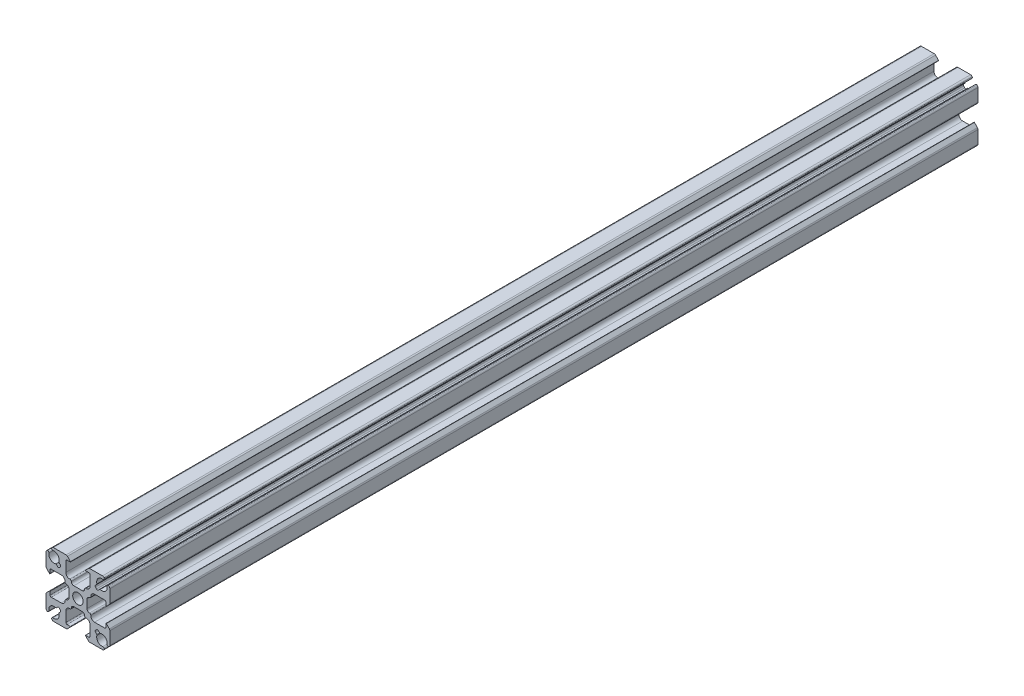
SolidWorks part; units mm, degrees
ref_plane "Front Plane" through (0, 0, 0) normal (0, 0, 1) x (1, 0, 0)
ref_plane "Top Plane" through (0, 0, 0) normal (0, 1, 0) x (1, 0, 0)
ref_plane "Right Plane" through (0, 0, 0) normal (1, 0, 0) x (0, 0, -1)
ref_plane "Plane1" through (0, 0, 0) normal (0, 0, -1) x (-1, 0, 0)
sketch "Sketch1" plane through (0, 0, 0) normal (0, 0, -1) x (-1, 0, 0)
  line L0 (-7.4885, 8.6199) -> (-6.9856, 8.117)
  line L1 (-6.9856, 7.4099) -> (-7.4099, 6.9856)
  line L2 (-8.117, 6.9856) -> (-8.6199, 7.4885)
  line L3 (-12.7, 9.7594) -> (-12.7, 4.7107)
  line L4 (-12.4803, 4.1803) -> (-11.2707, 2.9707)
  line L5 (-11.1, 3.0414) -> (-11.1, 4.325)
  line L6 (-10.6, 4.825) -> (-6.6, 4.825)
  line L7 (-5.1, 3.325) -> (-5.1, 3.15)
  line L8 (-3.6, 1.65) -> (-3.6, -1.65)
  line L9 (-5.1, -3.15) -> (-5.1, -3.325)
  line L10 (-6.6, -4.825) -> (-10.6, -4.825)
  line L11 (-11.1, -4.325) -> (-11.1, -3.0414)
  line L12 (-11.2707, -2.9707) -> (-12.4803, -4.1803)
  line L13 (-12.7, -4.7107) -> (-12.7, -9.7594)
  line L14 (-8.6199, -7.4885) -> (-8.117, -6.9856)
  line L15 (-7.4099, -6.9856) -> (-6.9856, -7.4099)
  line L16 (-6.9856, -8.117) -> (-7.4885, -8.6199)
  line L17 (-9.7594, -12.7) -> (-4.7107, -12.7)
  line L18 (-4.1803, -12.4803) -> (-2.9707, -11.2707)
  line L19 (-3.0414, -11.1) -> (-4.325, -11.1)
  line L20 (-4.825, -10.6) -> (-4.825, -6.6)
  line L21 (-3.325, -5.1) -> (-3.15, -5.1)
  line L22 (-1.65, -3.6) -> (1.65, -3.6)
  line L23 (3.15, -5.1) -> (3.325, -5.1)
  line L24 (4.825, -6.6) -> (4.825, -10.6)
  line L25 (4.325, -11.1) -> (3.0414, -11.1)
  line L26 (2.9707, -11.2707) -> (4.1803, -12.4803)
  line L27 (4.7107, -12.7) -> (9.7594, -12.7)
  line L28 (7.4885, -8.6199) -> (6.9856, -8.117)
  line L29 (6.9856, -7.4099) -> (7.4099, -6.9856)
  line L30 (8.117, -6.9856) -> (8.6199, -7.4885)
  line L31 (12.7, -9.7594) -> (12.7, -4.7107)
  line L32 (12.4803, -4.1803) -> (11.2707, -2.9707)
  line L33 (11.1, -3.0414) -> (11.1, -4.325)
  line L34 (10.6, -4.825) -> (6.6, -4.825)
  line L35 (5.1, -3.325) -> (5.1, -3.15)
  line L36 (3.6, -1.65) -> (3.6, 1.65)
  line L37 (5.1, 3.15) -> (5.1, 3.325)
  line L38 (6.6, 4.825) -> (10.6, 4.825)
  line L39 (11.1, 4.325) -> (11.1, 3.0414)
  line L40 (11.2707, 2.9707) -> (12.4803, 4.1803)
  line L41 (12.7, 4.7107) -> (12.7, 9.7594)
  line L42 (8.6199, 7.4885) -> (8.117, 6.9856)
  line L43 (7.4099, 6.9856) -> (6.9856, 7.4099)
  line L44 (6.9856, 8.117) -> (7.4885, 8.6199)
  line L45 (9.7594, 12.7) -> (4.7107, 12.7)
  line L46 (4.1803, 12.4803) -> (2.9707, 11.2707)
  line L47 (3.0414, 11.1) -> (4.325, 11.1)
  line L48 (4.825, 10.6) -> (4.825, 6.6)
  line L49 (3.325, 5.1) -> (3.15, 5.1)
  line L50 (1.65, 3.6) -> (-1.65, 3.6)
  line L51 (-3.15, 5.1) -> (-3.325, 5.1)
  line L52 (-4.825, 6.6) -> (-4.825, 10.6)
  line L53 (-4.325, 11.1) -> (-3.0414, 11.1)
  line L54 (-2.9707, 11.2707) -> (-4.1803, 12.4803)
  line L55 (-4.7107, 12.7) -> (-9.7594, 12.7)
  circle A0 centre (0, 0) radius 2.08
  arc A1 (-9.7594, 12.7) -> (-10.4266, 12.2927) centre (-9.7594, 11.95) ccw
  arc A2 (-10.4266, 12.2927) -> (-9.8933, 11.5721) centre (-9.9818, 12.0642) ccw
  arc A3 (-9.8933, 11.5721) -> (-7.5492, 8.8748) centre (-9.525, 9.525) cw
  arc A4 (-7.5492, 8.8748) -> (-7.4885, 8.6199) centre (-7.3118, 8.7967) ccw
  arc A5 (-6.9856, 8.117) -> (-6.9856, 7.4099) centre (-7.3392, 7.7635) cw
  arc A6 (-7.4099, 6.9856) -> (-8.117, 6.9856) centre (-7.7635, 7.3392) cw
  arc A7 (-8.6199, 7.4885) -> (-8.8748, 7.5492) centre (-8.7967, 7.3118) ccw
  arc A8 (-8.8748, 7.5492) -> (-11.5721, 9.8933) centre (-9.525, 9.525) cw
  arc A9 (-11.5721, 9.8933) -> (-12.2927, 10.4266) centre (-12.0642, 9.9818) ccw
  arc A10 (-12.2927, 10.4266) -> (-12.7, 9.7594) centre (-11.95, 9.7594) ccw
  arc A11 (-12.7, 4.7107) -> (-12.4803, 4.1803) centre (-11.95, 4.7107) ccw
  arc A12 (-11.2707, 2.9707) -> (-11.1, 3.0414) centre (-11.2, 3.0414) ccw
  arc A13 (-11.1, 4.325) -> (-10.6, 4.825) centre (-10.6, 4.325) cw
  arc A14 (-6.6, 4.825) -> (-5.1, 3.325) centre (-6.6, 3.325) cw
  arc A15 (-5.1, 3.15) -> (-4.6, 2.65) centre (-4.6, 3.15) ccw
  arc A16 (-4.6, 2.65) -> (-3.6, 1.65) centre (-4.6, 1.65) cw
  arc A17 (-3.6, -1.65) -> (-4.6, -2.65) centre (-4.6, -1.65) cw
  arc A18 (-4.6, -2.65) -> (-5.1, -3.15) centre (-4.6, -3.15) ccw
  arc A19 (-5.1, -3.325) -> (-6.6, -4.825) centre (-6.6, -3.325) cw
  arc A20 (-10.6, -4.825) -> (-11.1, -4.325) centre (-10.6, -4.325) cw
  arc A21 (-11.1, -3.0414) -> (-11.2707, -2.9707) centre (-11.2, -3.0414) ccw
  arc A22 (-12.4803, -4.1803) -> (-12.7, -4.7107) centre (-11.95, -4.7107) ccw
  arc A23 (-12.7, -9.7594) -> (-12.2927, -10.4266) centre (-11.95, -9.7594) ccw
  arc A24 (-12.2927, -10.4266) -> (-11.5721, -9.8933) centre (-12.0642, -9.9818) ccw
  arc A25 (-11.5721, -9.8933) -> (-8.8748, -7.5492) centre (-9.525, -9.525) cw
  arc A26 (-8.8748, -7.5492) -> (-8.6199, -7.4885) centre (-8.7967, -7.3118) ccw
  arc A27 (-8.117, -6.9856) -> (-7.4099, -6.9856) centre (-7.7635, -7.3392) cw
  arc A28 (-6.9856, -7.4099) -> (-6.9856, -8.117) centre (-7.3392, -7.7635) cw
  arc A29 (-7.4885, -8.6199) -> (-7.5492, -8.8748) centre (-7.3118, -8.7967) ccw
  arc A30 (-7.5492, -8.8748) -> (-9.8933, -11.5721) centre (-9.525, -9.525) cw
  arc A31 (-9.8933, -11.5721) -> (-10.4266, -12.2927) centre (-9.9818, -12.0642) ccw
  arc A32 (-10.4266, -12.2927) -> (-9.7594, -12.7) centre (-9.7594, -11.95) ccw
  arc A33 (-4.7107, -12.7) -> (-4.1803, -12.4803) centre (-4.7107, -11.95) ccw
  arc A34 (-2.9707, -11.2707) -> (-3.0414, -11.1) centre (-3.0414, -11.2) ccw
  arc A35 (-4.325, -11.1) -> (-4.825, -10.6) centre (-4.325, -10.6) cw
  arc A36 (-4.825, -6.6) -> (-3.325, -5.1) centre (-3.325, -6.6) cw
  arc A37 (-3.15, -5.1) -> (-2.65, -4.6) centre (-3.15, -4.6) ccw
  arc A38 (-2.65, -4.6) -> (-1.65, -3.6) centre (-1.65, -4.6) cw
  arc A39 (1.65, -3.6) -> (2.65, -4.6) centre (1.65, -4.6) cw
  arc A40 (2.65, -4.6) -> (3.15, -5.1) centre (3.15, -4.6) ccw
  arc A41 (3.325, -5.1) -> (4.825, -6.6) centre (3.325, -6.6) cw
  arc A42 (4.825, -10.6) -> (4.325, -11.1) centre (4.325, -10.6) cw
  arc A43 (3.0414, -11.1) -> (2.9707, -11.2707) centre (3.0414, -11.2) ccw
  arc A44 (4.1803, -12.4803) -> (4.7107, -12.7) centre (4.7107, -11.95) ccw
  arc A45 (9.7594, -12.7) -> (10.4266, -12.2927) centre (9.7594, -11.95) ccw
  arc A46 (10.4266, -12.2927) -> (9.8933, -11.5721) centre (9.9818, -12.0642) ccw
  arc A47 (9.8933, -11.5721) -> (7.5492, -8.8748) centre (9.525, -9.525) cw
  arc A48 (7.5492, -8.8748) -> (7.4885, -8.6199) centre (7.3118, -8.7967) ccw
  arc A49 (6.9856, -8.117) -> (6.9856, -7.4099) centre (7.3392, -7.7635) cw
  arc A50 (7.4099, -6.9856) -> (8.117, -6.9856) centre (7.7635, -7.3392) cw
  arc A51 (8.6199, -7.4885) -> (8.8748, -7.5492) centre (8.7967, -7.3118) ccw
  arc A52 (8.8748, -7.5492) -> (11.5721, -9.8933) centre (9.525, -9.525) cw
  arc A53 (11.5721, -9.8933) -> (12.2927, -10.4266) centre (12.0642, -9.9818) ccw
  arc A54 (12.2927, -10.4266) -> (12.7, -9.7594) centre (11.95, -9.7594) ccw
  arc A55 (12.7, -4.7107) -> (12.4803, -4.1803) centre (11.95, -4.7107) ccw
  arc A56 (11.2707, -2.9707) -> (11.1, -3.0414) centre (11.2, -3.0414) ccw
  arc A57 (11.1, -4.325) -> (10.6, -4.825) centre (10.6, -4.325) cw
  arc A58 (6.6, -4.825) -> (5.1, -3.325) centre (6.6, -3.325) cw
  arc A59 (5.1, -3.15) -> (4.6, -2.65) centre (4.6, -3.15) ccw
  arc A60 (4.6, -2.65) -> (3.6, -1.65) centre (4.6, -1.65) cw
  arc A61 (3.6, 1.65) -> (4.6, 2.65) centre (4.6, 1.65) cw
  arc A62 (4.6, 2.65) -> (5.1, 3.15) centre (4.6, 3.15) ccw
  arc A63 (5.1, 3.325) -> (6.6, 4.825) centre (6.6, 3.325) cw
  arc A64 (10.6, 4.825) -> (11.1, 4.325) centre (10.6, 4.325) cw
  arc A65 (11.1, 3.0414) -> (11.2707, 2.9707) centre (11.2, 3.0414) ccw
  arc A66 (12.4803, 4.1803) -> (12.7, 4.7107) centre (11.95, 4.7107) ccw
  arc A67 (12.7, 9.7594) -> (12.2927, 10.4266) centre (11.95, 9.7594) ccw
  arc A68 (12.2927, 10.4266) -> (11.5721, 9.8933) centre (12.0642, 9.9818) ccw
  arc A69 (11.5721, 9.8933) -> (8.8748, 7.5492) centre (9.525, 9.525) cw
  arc A70 (8.8748, 7.5492) -> (8.6199, 7.4885) centre (8.7967, 7.3118) ccw
  arc A71 (8.117, 6.9856) -> (7.4099, 6.9856) centre (7.7635, 7.3392) cw
  arc A72 (6.9856, 7.4099) -> (6.9856, 8.117) centre (7.3392, 7.7635) cw
  arc A73 (7.4885, 8.6199) -> (7.5492, 8.8748) centre (7.3118, 8.7967) ccw
  arc A74 (7.5492, 8.8748) -> (9.8933, 11.5721) centre (9.525, 9.525) cw
  arc A75 (9.8933, 11.5721) -> (10.4266, 12.2927) centre (9.9818, 12.0642) ccw
  arc A76 (10.4266, 12.2927) -> (9.7594, 12.7) centre (9.7594, 11.95) ccw
  arc A77 (4.7107, 12.7) -> (4.1803, 12.4803) centre (4.7107, 11.95) ccw
  arc A78 (2.9707, 11.2707) -> (3.0414, 11.1) centre (3.0414, 11.2) ccw
  arc A79 (4.325, 11.1) -> (4.825, 10.6) centre (4.325, 10.6) cw
  arc A80 (4.825, 6.6) -> (3.325, 5.1) centre (3.325, 6.6) cw
  arc A81 (3.15, 5.1) -> (2.65, 4.6) centre (3.15, 4.6) ccw
  arc A82 (2.65, 4.6) -> (1.65, 3.6) centre (1.65, 4.6) cw
  arc A83 (-1.65, 3.6) -> (-2.65, 4.6) centre (-1.65, 4.6) cw
  arc A84 (-2.65, 4.6) -> (-3.15, 5.1) centre (-3.15, 4.6) ccw
  arc A85 (-3.325, 5.1) -> (-4.825, 6.6) centre (-3.325, 6.6) cw
  arc A86 (-4.825, 10.6) -> (-4.325, 11.1) centre (-4.325, 10.6) cw
  arc A87 (-3.0414, 11.1) -> (-2.9707, 11.2707) centre (-3.0414, 11.2) ccw
  arc A88 (-4.1803, 12.4803) -> (-4.7107, 12.7) centre (-4.7107, 11.95) ccw
extrude "Boss-Extrude1" add sketch "Sketch1" against normal mid plane 345.1098
hole_wizard "Tap Drill for M6x1.0 Tap2" positions "Sketch3" profile "Sketch2" hole size "M6x1.0" standard "ANSI Metric" end condition through all
sketch "Sketch3" plane through (3.6, 0, 0) normal (1, 0, 0) x (0, 0, -1)
  point P0 (-120.8849, -4.45)
  point P3 (15.0051, -4.45)
  point P6 (-120.8849, -4.45)
sketch "Sketch2" plane through (3.6, -4.45, 120.8849) normal (0, 1, 0) x (0, 0, -1)
  line L0 (0, 0) -> (0, 16.3)
  line L1 (0, 16.3) -> (2.5, 16.3)
  line L2 (2.5, 16.3) -> (2.5, 0)
  line L5 (2.5, 0) -> (0, 0)
  line L11 (0, -6.35) -> (0, 107.95) construction
  dimension "Thru Hole Dia." = 5
  dimension "Thru Hole Depth" = 16.3
hole_wizard "Tap Drill for M6x1.0 Tap1" positions "Sketch5" profile "Sketch4" hole size "M6x1.0" standard "ANSI Metric" end condition through all
sketch "Sketch5" plane through (-3.6, 0, 0) normal (-1, 0, 0) x (0, 0, 1)
  point P0 (151.6049, 0)
  point P3 (31.6049, 0)
  point P6 (-88.3951, 0)
sketch "Sketch4" plane through (-3.6, 0, 151.6049) normal (0, 1, 0) x (0, 0, 1)
  line L0 (0, 0) -> (0, 16.3)
  line L1 (0, 16.3) -> (2.5, 16.3)
  line L2 (2.5, 16.3) -> (2.5, 0)
  line L5 (2.5, 0) -> (0, 0)
  line L11 (0, -6.35) -> (0, 107.95) construction
  dimension "Thru Hole Dia." = 5
  dimension "Thru Hole Depth" = 16.3
